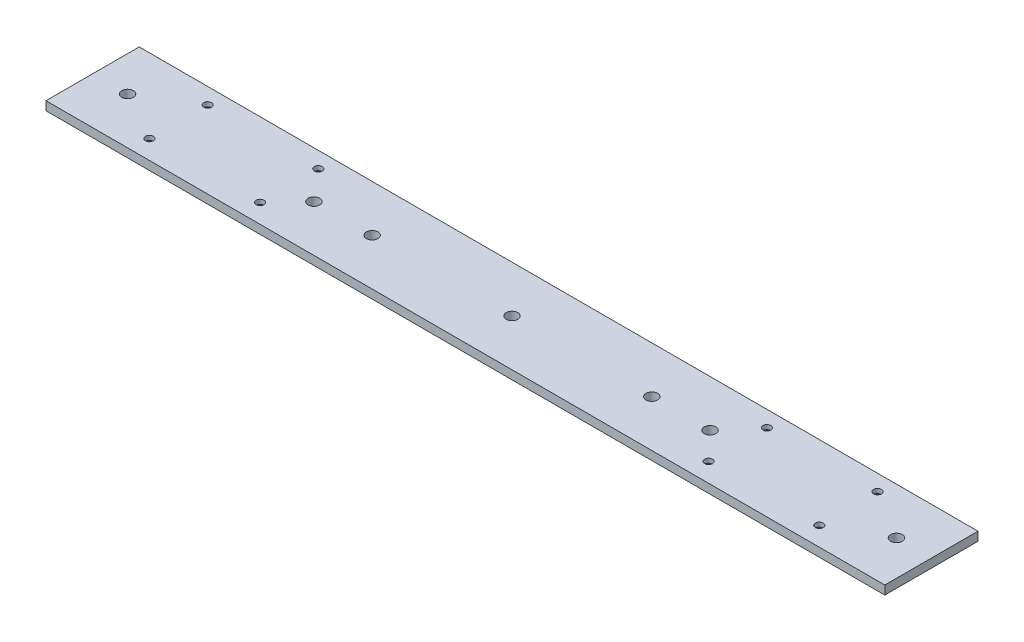
SolidWorks part; units mm, degrees
material "6061 Alloy"
ref_plane "Front Plane" through (0, 0, 0) normal (0, 0, 1) x (1, 0, 0)
ref_plane "Top Plane" through (0, 0, 0) normal (0, 1, 0) x (1, 0, 0)
ref_plane "Right Plane" through (0, 0, 0) normal (1, 0, 0) x (0, 0, -1)
sketch "Sketch1" plane through (0, 0, 0) normal (0, 1, 0) x (1, 0, 0)
  line L1 (0, 0) -> (457.2, 0)
  line L2 (0, 0) -> (0, 50.8)
  line L3 (0, 50.8) -> (457.2, 50.8)
  line L4 (457.2, 0) -> (457.2, 50.8)
  dimension "D1" = 457.2
  dimension "D2" = 50.8
extrude "Boss-Extrude1" add sketch "Sketch1" along normal blind 4.7625
sketch "Sketch2" plane through (0, 4.7625, 0) normal (0, 1, 0) x (1, 0, 0)
  line L0 (0, 0) -> (457.2, 0) construction
  line L1 (0, 50.8) -> (0, 0) construction
  circle A0 centre (19.05, 25.4) radius 3.175
  circle A1 centre (438.15, 25.4) radius 3.175
  dimension "D1" = 25.4
  dimension "D2" = 25.4
  dimension "D3" = 19.05
  dimension "D4" = 438.15
extrude "Cut-Extrude1" cut sketch "Sketch2" against normal blind 244.602
sketch "Sketch3" plane through (0, 4.7625, 0) normal (0, 1, 0) x (1, 0, 0)
  line L0 (457.2, 50.8) -> (0, 50.8) construction
  line L1 (457.2, 0) -> (457.2, 50.8) construction
  circle A0 centre (152.4, 25.4) radius 3.175
  circle A1 centre (304.8, 25.4) radius 3.175
  circle A2 centre (228.6, 25.4) radius 3.175
  dimension "D1" = 25.4
  dimension "D2" = 25.4
  dimension "D3" = 25.4
  dimension "D4" = 76.2
  dimension "D5" = 228.6
  dimension "D6" = 76.2
extrude "Cut-Extrude2" cut sketch "Sketch3" against normal blind 244.602
sketch "Sketch4" plane through (0, 4.7625, 0) normal (0, 1, 0) x (1, 0, 0)
  line L0 (457.2, 50.8) -> (0, 50.8) construction
  line L1 (0, 50.8) -> (0, 0) construction
  line L2 (457.2, 0) -> (457.2, 50.8) construction
  circle A0 centre (120.65, 25.4) radius 3.175
  circle A1 centre (336.55, 25.4) radius 3.175
  dimension "D1" = 25.4
  dimension "D4" = 120.65
  dimension "D2" = 25.4
  dimension "D3" = 120.65
extrude "Cut-Extrude3" cut sketch "Sketch4" against normal blind 25.4
hole_wizard "CSK for #8 Flat Head Machine Screw1" positions "Sketch7" profile "Sketch5" countersink size "#8" standard "ANSI Inch" end condition through all
sketch "Sketch7" plane through (0, 0, 0) normal (0, -1, 0) x (-1, 0, 0)
  point P0 (-46.0375, 42.0688)
  point P3 (-46.0375, 10.3188)
  point P6 (-106.3625, 10.3188)
  point P9 (-106.3625, 42.0688)
  point P12 (-350.8375, 42.0688)
  point P15 (-350.8375, 10.3188)
  point P18 (-411.1625, 10.3188)
  point P21 (-411.1625, 42.0688)
sketch "Sketch5" plane through (46.0375, 0, -42.0688) normal (1, 0, 0) x (0, 0, -1)
  line L0 (0, 0) -> (0, 4.7625)
  line L1 (0, 4.7625) -> (2.1526, 4.7625)
  line L2 (2.1526, 4.7625) -> (2.1526, 2.3741)
  line L3 (2.1526, 2.3741) -> (4.2164, 0)
  line L5 (4.2164, 0) -> (0, 0)
  line L6 (-2.1527, 2.3741) -> (-4.2164, 0) construction
  line L11 (0, -6.35) -> (0, 107.95) construction
  dimension "Thru Hole Dia." = 4.3053
  dimension "Thru Hole Depth" = 4.7625
  dimension "Near C'Sink Dia." = 8.4328
  dimension "Near C'Sink Angle" = 82
